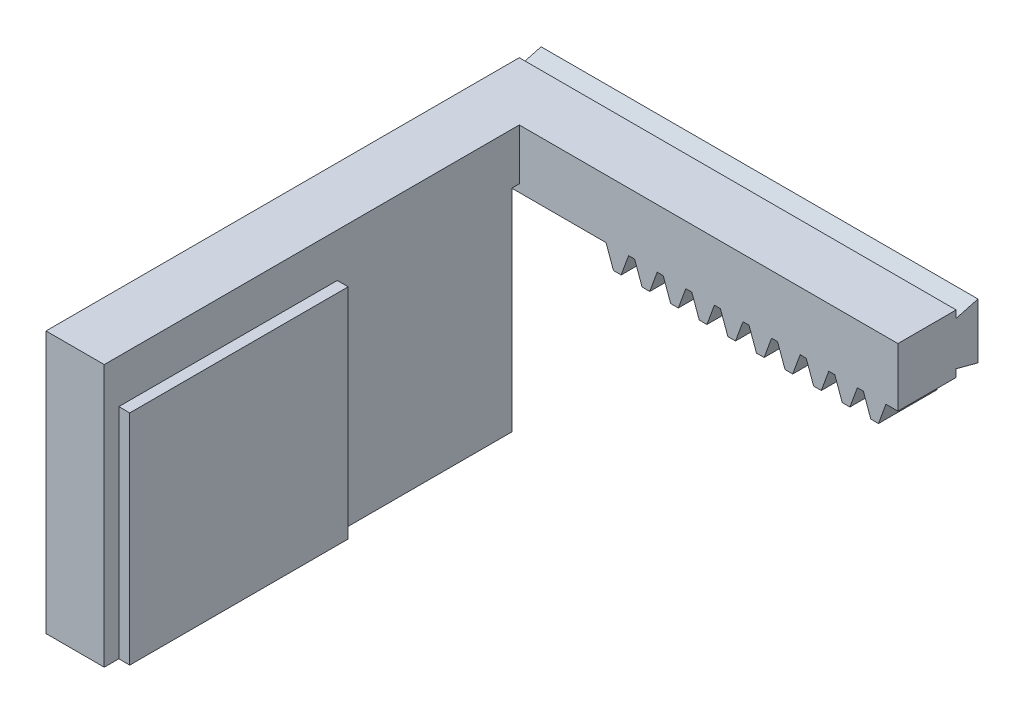
SolidWorks part; units mm, degrees
ref_plane "Front Plane" through (0, 0, 0) normal (0, 0, 1) x (1, 0, 0)
ref_plane "Top Plane" through (0, 0, 0) normal (0, 1, 0) x (1, 0, 0)
ref_plane "Right Plane" through (0, 0, 0) normal (1, 0, 0) x (0, 0, -1)
sketch "Rack profile m1.25" plane through (0, 0, 0) normal (0, 0, 1) x (1, 0, 0)
  line L0 (-8, 21) -> (52, 21)
  line L1 (52, 21) -> (52, 12.9625)
  line L2 (52, 12.9625) -> (50.3569, 12.9625)
  line L3 (50.3569, 12.9625) -> (49.3332, 10.15)
  line L4 (49.3332, 10.15) -> (48.2796, 10.15)
  line L5 (48.2796, 10.15) -> (47.256, 12.9625)
  line L6 (47.256, 12.9625) -> (46.4299, 12.9625)
  line L7 (46.4299, 12.9625) -> (45.4062, 10.15)
  line L8 (45.4062, 10.15) -> (44.3526, 10.15)
  line L9 (44.3526, 10.15) -> (43.329, 12.9625)
  line L10 (43.329, 12.9625) -> (42.5029, 12.9625)
  line L11 (42.5029, 12.9625) -> (41.4792, 10.15)
  line L12 (41.4792, 10.15) -> (40.4256, 10.15)
  line L13 (40.4256, 10.15) -> (39.402, 12.9625)
  line L14 (39.402, 12.9625) -> (38.5759, 12.9625)
  line L15 (38.5759, 12.9625) -> (37.5522, 10.15)
  line L16 (37.5522, 10.15) -> (36.4987, 10.15)
  line L17 (36.4987, 10.15) -> (35.475, 12.9625)
  line L18 (35.475, 12.9625) -> (34.6489, 12.9625)
  line L19 (34.6489, 12.9625) -> (33.6252, 10.15)
  line L20 (33.6252, 10.15) -> (32.5717, 10.15)
  line L21 (32.5717, 10.15) -> (31.548, 12.9625)
  line L22 (31.548, 12.9625) -> (30.7219, 12.9625)
  line L23 (30.7219, 12.9625) -> (29.6982, 10.15)
  line L24 (29.6982, 10.15) -> (28.6447, 10.15)
  line L25 (28.6447, 10.15) -> (27.621, 12.9625)
  line L26 (27.621, 12.9625) -> (26.7949, 12.9625)
  line L27 (26.7949, 12.9625) -> (25.7713, 10.15)
  line L28 (25.7713, 10.15) -> (24.7177, 10.15)
  line L29 (24.7177, 10.15) -> (23.694, 12.9625)
  line L30 (23.694, 12.9625) -> (22.8679, 12.9625)
  line L31 (22.8679, 12.9625) -> (21.8443, 10.15)
  line L32 (21.8443, 10.15) -> (20.7907, 10.15)
  line L33 (20.7907, 10.15) -> (19.767, 12.9625)
  line L34 (19.767, 12.9625) -> (18.9409, 12.9625)
  line L35 (18.9409, 12.9625) -> (17.9173, 10.15)
  line L36 (17.9173, 10.15) -> (16.8637, 10.15)
  line L37 (16.8637, 10.15) -> (15.84, 12.9625)
  line L38 (15.84, 12.9625) -> (15.0139, 12.9625)
  line L39 (15.0139, 12.9625) -> (13.9903, 10.15)
  line L40 (13.9903, 10.15) -> (12.9367, 10.15)
  line L41 (12.9367, 10.15) -> (11.913, 12.9625)
  line L42 (11.913, 12.9625) -> (-8, 12.9625)
  line L43 (-8, 12.9625) -> (-8, 21)
extrude "Rack body 8mm" add sketch "Rack profile m1.25" along normal blind 8 contours L0 L1 L2 L3 L4 L5 L6 L7 L8 L9 L10 L11 L12 L13 L14 L15 L16 L17 L18 L19 L20 L21 L22 L23 L24 L25 L26 L27 L28 L29 L30 L31 L32 L33 L34 L35 L36 L37 L38 L39 L40 L41 L42 L43
sketch "Finger Arm Profile" plane through (0, 0, 0) normal (1, 0, 0) x (0, 0, -1)
  line L0 (-2, 21) -> (-65, 21)
  line L1 (-65, 21) -> (-65, -15)
  line L2 (-65, -15) -> (-9, -15)
  line L3 (-9, -15) -> (-9, 14)
  line L4 (-9, 14) -> (-2, 14)
  line L5 (-2, 14) -> (-2, 21)
extrude "Finger arm 8mm" add sketch "Finger Arm Profile" against normal blind 8
sketch "Dovetail Tongue" plane through (0, 0, 0) normal (1, 0, 0) x (0, 0, -1)
  line L0 (0, 14) -> (0, 20)
  line L1 (0, 20) -> (3, 20.8)
  line L2 (3, 20.8) -> (3, 13.2)
  line L3 (3, 13.2) -> (0, 14)
extrude "Dovetail Tongue 52 + 8" add sketch "Dovetail Tongue" along normal blind 52 and the other way blind 8
sketch "Sensor Pocket Placeholder" plane through (0, 0, 0) normal (1, 0, 0) x (0, 0, -1)
  circle A0 centre (-48, 0) radius 10
extrude "Sensor Pocket Cut" cut sketch "Sensor Pocket Placeholder" against normal blind 1.5
sketch "Neoprened pad sketch" plane through (0, 0, 0) normal (1, 0, 0) x (0, 0, -1)
  line L0 (-33, -15) -> (-63, -15)
  line L1 (-63, -15) -> (-63, 15)
  line L2 (-63, 15) -> (-33, 15)
  line L3 (-33, 15) -> (-33, -15)
extrude "Neoprene pad (not printed)" add sketch "Neoprened pad sketch" along normal blind 1.5 separate body
